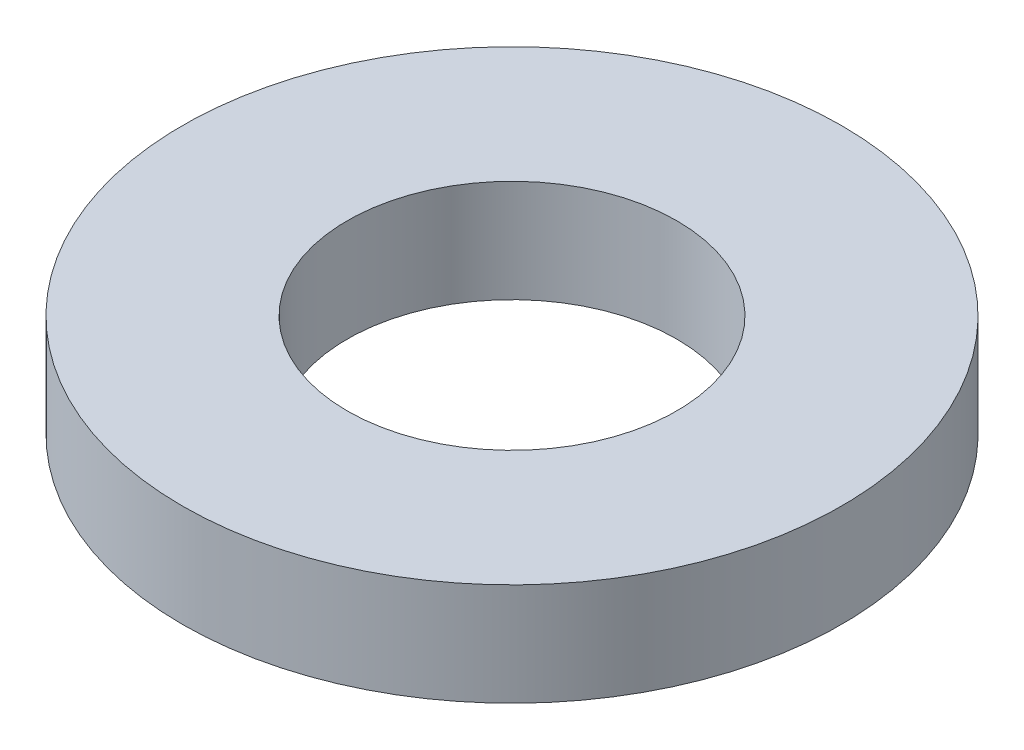
SolidWorks part; units mm, degrees
ref_plane "Front Plane" through (0, 0, 0) normal (0, 0, 1) x (1, 0, 0)
ref_plane "Top Plane" through (0, 0, 0) normal (0, 1, 0) x (1, 0, 0)
ref_plane "Right Plane" through (0, 0, 0) normal (1, 0, 0) x (0, 0, -1)
sketch "Sketch1" plane through (0, 0, 0) normal (0, 1, 0) x (1, 0, 0)
  circle A0 centre (0, 0) radius 45
  dimension "FLANGE_OD" = 90
extrude "Boss-Extrude1" add sketch "Sketch1" along normal blind 14
sketch "Sketch2" plane through (0, 0, 0) normal (0, 1, 0) x (1, 0, 0)
  circle A0 centre (0, 0) radius 22.5
  dimension "BORE_D" = 45
extrude "Cut-Extrude1" cut sketch "Sketch2" along normal through all
sketch "Sketch3" plane through (0, 14, 0) normal (0, 1, 0) x (1, 0, 0)
  circle A0 centre (0, 0) radius 18.4454 construction
  circle A1 centre (-18.4454, 0) radius 2.8451
  dimension "BOLT_D" = 5.6902
  dimension "BOLT_PCD" = 36.8909
extrude "Cut-Extrude2" cut sketch "Sketch3" against normal blind 10.9109 rebuild error yes
pattern_circular "CirPattern1" count 8 over 360 rebuild error yes
